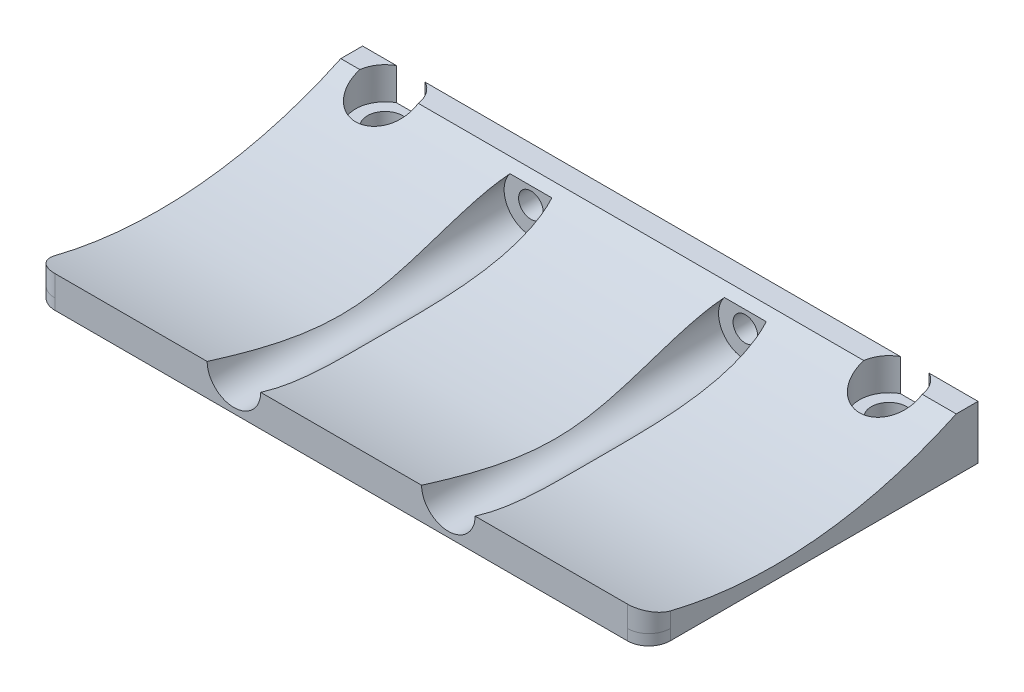
SolidWorks part; units mm, degrees
ref_plane "Front Plane" through (0, 0, 0) normal (0, 0, 1) x (1, 0, 0)
ref_plane "Top Plane" through (0, 0, 0) normal (0, 1, 0) x (1, 0, 0)
ref_plane "Right Plane" through (0, 0, 0) normal (1, 0, 0) x (0, 0, -1)
sketch "Sketch1" plane through (0, 0, 0) normal (0, 1, 0) x (1, 0, 0)
  line L0 (4.5, 28.3) -> (4.5, 4.7) construction
  line L1 (0, 0) -> (57.4, 0)
  line L2 (0, 0) -> (0, 33)
  line L3 (0, 33) -> (57.4, 33)
  line L4 (57.4, 0) -> (57.4, 33)
  circle A0 centre (4.5, 28.3) radius 1.65
  circle A1 centre (51.5, 28.3) radius 1.65
  circle A2 centre (4.5, 4.7) radius 1.65
  circle A3 centre (51.5, 4.7) radius 1.65
  point P13 (0, 16.5)
  point P14 (4.5, 16.5)
  dimension "D3" = 3.3
  dimension "D4" = 47
  dimension "D5" = 23.6
  dimension "D6" = 4.5
  dimension "D1" = 57.4
  dimension "D2" = 33
extrude "Boss-Extrude1" add sketch "Sketch1" along normal blind 1
sketch "Sketch2" plane through (0, 1, 0) normal (0, 1, 0) x (1, 0, 0)
  line L0 (57.4, 0) -> (57.4, 33) construction
  line L1 (0, 33) -> (57.4, 33)
  line L2 (0, 33) -> (0, 30.7)
  line L3 (0, 30.7) -> (57.4, 30.7)
  line L4 (57.4, 33) -> (57.4, 30.7)
  dimension "D1" = 2.3
extrude "Cut-Extrude1" cut sketch "Sketch2" against normal up to next
sketch "Sketch3" plane through (57.4, 0, 0) normal (1, 0, 0) x (0, 0, -1)
  line L0 (30.7, 1) -> (30.7, 5)
  line L1 (30.7, 5) -> (28.7, 5)
  line L2 (28.7, 5) -> (20.7, 1)
  line L3 (0, 1) -> (30.7, 1) construction
  line L4 (20.7, 1) -> (30.7, 1)
  dimension "D1" = 4
  dimension "D2" = 10
  dimension "D3" = 2
extrude "Boss-Extrude2" add sketch "Sketch3" against normal up to surface (57.4 mm away) up to face at (0, 0.5, -15.35)
fillet "Fillet1" radius 2 2 edges at (0, 0.5, 0) (57.4, 0.5, 0)
sketch "Sketch10" plane through (0, 0, 0) normal (1, 0, 0) x (0, 0, -1)
  line L0 (2, 1) -> (0, 1) construction
  line L1 (0, 1) -> (0, 0) construction
  line L2 (0, 0) -> (2, 0) construction
  line L3 (20.7, 1) -> (2, 1) construction
  line L4 (2, 0) -> (30.7, 0) construction
  line L5 (30.7, 0) -> (30.7, 5) construction
  line L6 (30.7, 5) -> (28.7, 5) construction
  line L7 (28.7, 5) -> (20.7, 1) construction
  line L8 (2, 1) -> (0, 1)
  line L9 (0, 1) -> (0, 0)
  line L10 (0, 0) -> (2, 0)
  line L11 (20.7, 1) -> (2, 1)
  line L12 (2, 0) -> (30.7, 0)
  line L13 (30.7, 0) -> (30.7, 5)
  line L14 (30.7, 5) -> (28.7, 5)
  line L15 (28.7, 5) -> (20.7, 1)
  line L16 (0, 1) -> (0, 2.9741)
  line L17 (28.7, 5) -> (28.6687, 5)
  circle A0 centre (11.703, 41.2238) radius 40
  point P2 (0, 0)
  point P3 (0, 0)
  dimension "D1" = 80
extrude "Boss-Extrude3" add sketch "Sketch10" along direction (-1, 0, 0) on the side of the normal up to surface (57.4 mm away) contours A0 L16 L8 L11 L15 L17 region at (0, 1.2898, -1) up to face at (57.4, 2, -19.1333)
sketch "Sketch4" plane through (0, 0, 0) normal (0, -1, 0) x (-1, 0, 0)
  circle A0 centre (-4.5, 28.3) radius 1.65
  circle A1 centre (-51.5, 28.3) radius 1.65
  dimension "D1" = 3.3
extrude "Cut-Extrude2" cut sketch "Sketch4" against normal blind 2
sketch "Sketch5" plane through (0, 2, 0) normal (0, -1, 0) x (-1, 0, 0)
  circle A0 centre (-4.5, 28.3) radius 2.75
  circle A1 centre (-51.5, 28.3) radius 2.75
  dimension "D1" = 5.5
extrude "Cut-Extrude3" cut sketch "Sketch5" against normal up to next
sketch "Sketch6" plane through (0, 0, -30.7) normal (0, 0, -1) x (-1, 0, 0)
  circle A0 centre (-38.7, 3) radius 1.15
  circle A1 centre (-18.7, 3) radius 1.15
  dimension "D1" = 2.3
extrude "Cut-Extrude4" cut sketch "Sketch6" against normal blind 3
sketch "Sketch9" plane through (0, 0, -27.7) normal (0, 0, -1) x (-1, 0, 0)
  circle A0 centre (-38.7, 3) radius 2.5
  circle A1 centre (-18.7, 3) radius 2.5
  dimension "D1" = 5
extrude "Cut-Extrude5" cut sketch "Sketch9" against normal through all
fillet "Fillet2" radius 2 2 edges at (0, 1.9871, 0) (57.4, 1.9871, 0)
